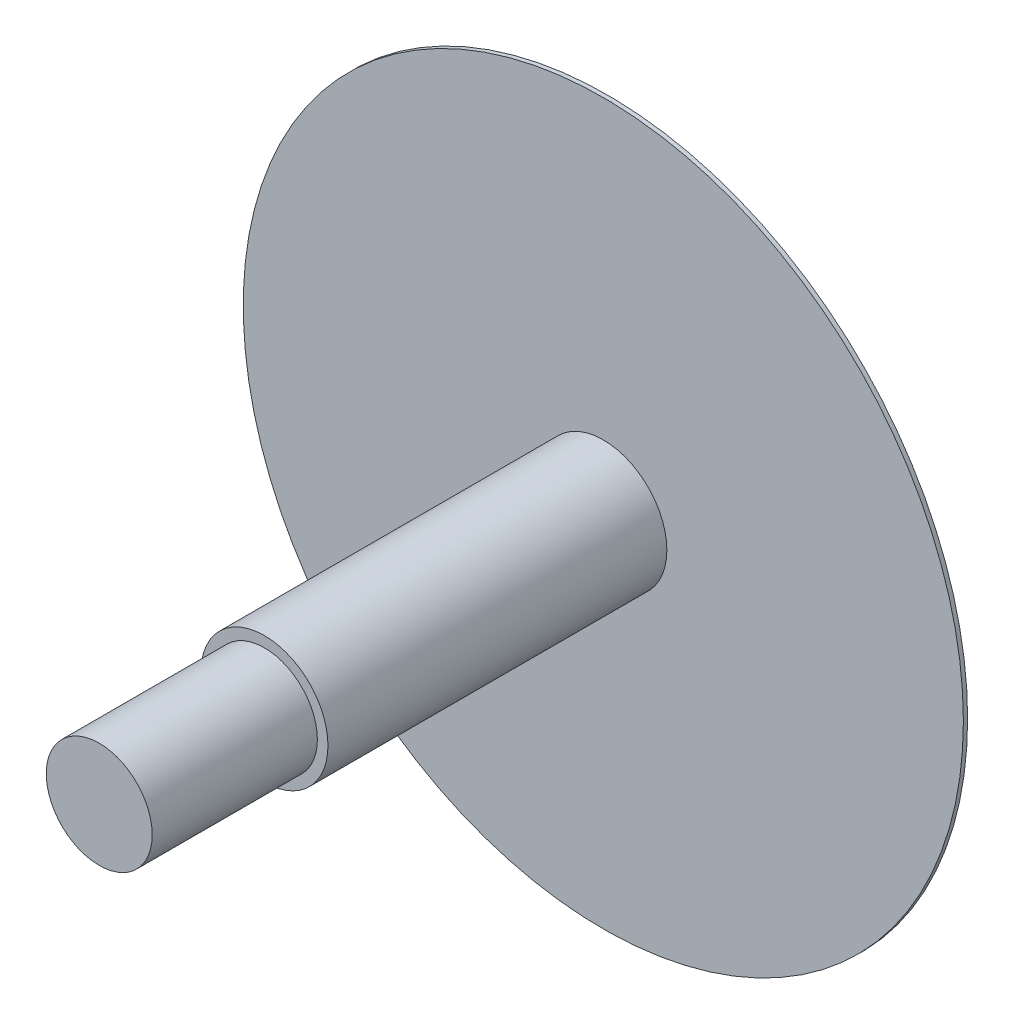
SolidWorks part; units mm, degrees
ref_plane "前视基准面" through (0, 0, 0) normal (0, 0, 1) x (1, 0, 0)
ref_plane "上视基准面" through (0, 0, 0) normal (0, 1, 0) x (1, 0, 0)
ref_plane "右视基准面" through (0, 0, 0) normal (1, 0, 0) x (0, 0, -1)
sketch "草图1" plane through (0, 0, 0) normal (0, 0, 1) x (1, 0, 0)
  circle A0 centre (0, 0) radius 85
  circle A1 centre (0, 0) radius 15
  circle A2 centre (0, 0) radius 12.5
extrude "凸台-拉伸1" add sketch "草图1" along normal blind 1 contours A0 A1 region at (-82.5958, 0, 0)
extrude "凸台-拉伸2" add sketch "草图1<3>" along normal blind 81 from offset 0 contours A2 | A1 A2 region at (-14.5757, 0, 0) region at (0, 0, 0)
sketch "草图1<3>" plane through (0, 0, 0) normal (0, 0, 1) x (1, 0, 0) same geometry as "草图1"
extrude "凸台-拉伸3" add sketch "草图1<4>" along normal blind 120 contours A2 region at (0, 0, 0)
sketch "草图1<4>" plane through (0, 0, 0) normal (0, 0, 1) x (1, 0, 0) same geometry as "草图1"
